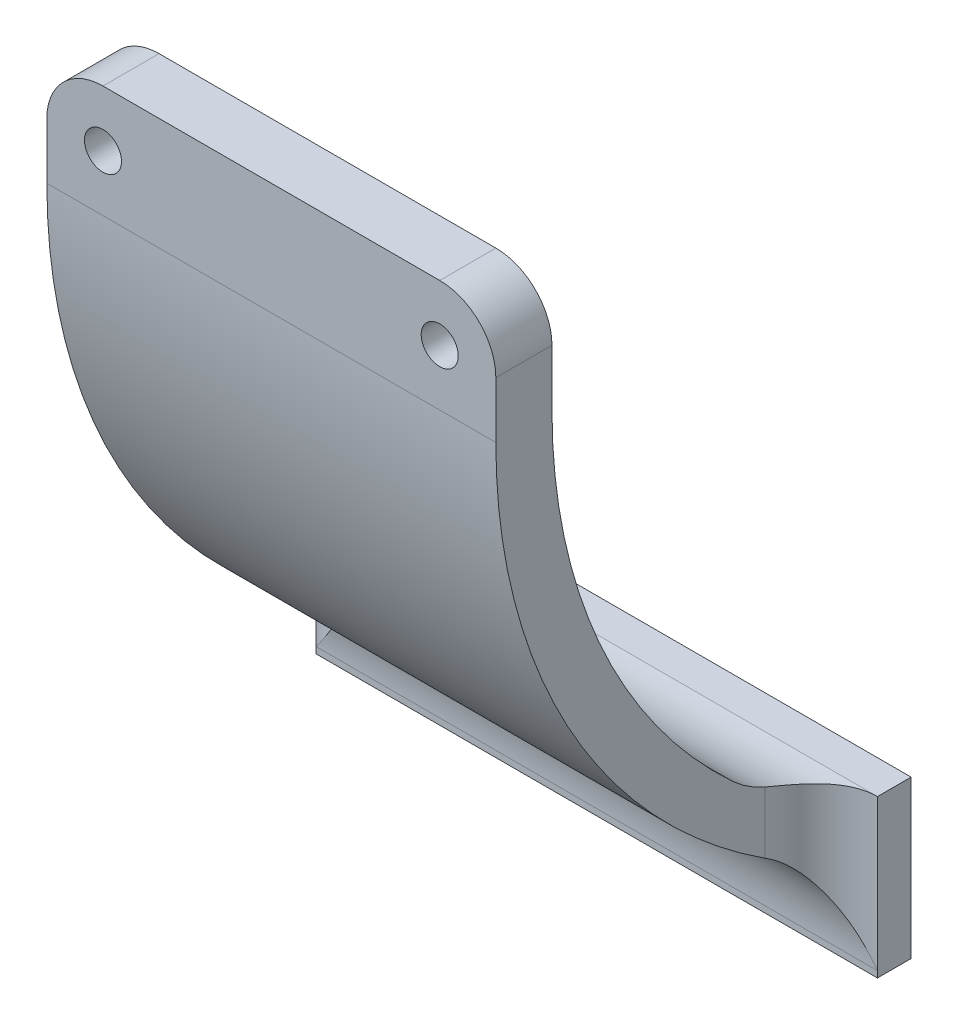
SolidWorks part; units mm, degrees
material "ABS"
ref_plane "前视基准面" through (0, 0, 0) normal (0, 0, 1) x (1, 0, 0)
ref_plane "上视基准面" through (0, 0, 0) normal (0, 1, 0) x (1, 0, 0)
ref_plane "右视基准面" through (0, 0, 0) normal (1, 0, 0) x (0, 0, -1)
other "Configuration Table"
sketch "草图1" plane through (0, 0, 0) normal (0, 0, 1) x (1, 0, 0)
  line L0 (0, 0) -> (30, 0) construction
  line L1 (-5, 0) -> (0, 0) construction
  line L2 (-5, 5) -> (35, 5)
  line L3 (-5, 5) -> (-5, -5)
  line L4 (-5, -5) -> (35, -5)
  line L5 (35, 5) -> (35, -5)
  line L6 (15, 0) -> (15, 5) construction
  circle A0 centre (0, 0) radius 1.65
  circle A1 centre (30, 0) radius 1.65
  point P13 (0, 0)
  point P14 (0, 0)
  point P15 (0.2219, 0.2498)
  dimension "D2" = 3.3
  dimension "D4" = 5
  dimension "D1" = 30
  dimension "D3" = 5
extrude "凸台-拉伸1" add sketch "草图1" along normal blind 5
sketch "草图2" plane through (35, 0, 0) normal (1, 0, 0) x (0, 0, -1)
  line L0 (27, -53.3198) -> (27, -49.3198)
  line L1 (-5, -5) -> (-5, 5) construction
  line L2 (0, -5) -> (0, 5) construction
  line L3 (-5, -5) -> (0, -5)
  arc A0 (-5, -5) -> (27, -53.3198) centre (47.4813, -5) ccw
  arc A1 (0, -5) -> (27, -49.3198) centre (49.8749, -5) ccw
  dimension "D1" = 32
  dimension "D2" = 4
extrude "凸台-拉伸2" add sketch "草图2" against normal up to surface (40 mm away) up to face at (-5, 0, 2.5)
sketch "草图3" plane through (0, 0, -27) normal (0, 0, -1) x (-1, 0, 0)
  line L8 (10, -58.3198) -> (10, -44.3198)
  line L9 (10, -44.3198) -> (-40, -44.3198)
  line L10 (-40, -44.3198) -> (-40, -58.3198)
  line L11 (-40, -58.3198) -> (10, -58.3198)
  line L12 (10, -58.3198) -> (10, -44.3198)
  line L13 (10, -44.3198) -> (-40, -44.3198)
  line L14 (-40, -44.3198) -> (-40, -58.3198)
  line L15 (-40, -58.3198) -> (10, -58.3198)
  dimension "D1" = 5
extrude "凸台-拉伸3" add sketch "草图3" against normal blind 3
fillet "圆角1" radius 10 2 edges at (15, -47.6379, -24) (15, -51.9352, -24)
fillet "圆角2" radius 5 4 edges at (35, 5, 2.5) (-5, 5, 2.5) (35, -51.0366, -24) (-5, -51.0366, -24)
